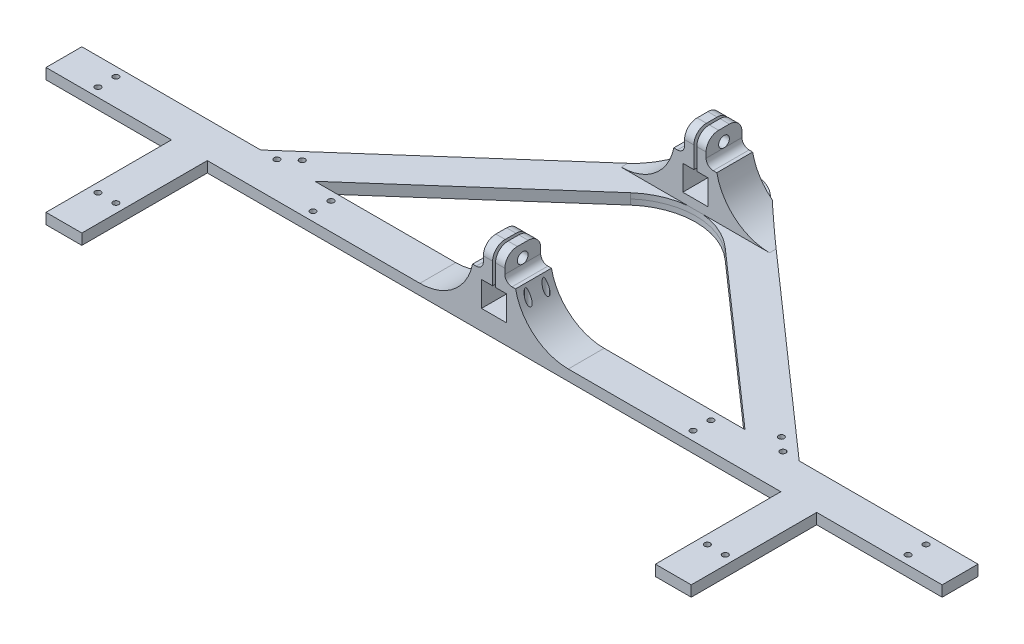
SolidWorks part; units mm, degrees
ref_plane "前视基准面" through (0, 0, 0) normal (0, 0, 1) x (1, 0, 0)
ref_plane "上视基准面" through (0, 0, 0) normal (0, 1, 0) x (1, 0, 0)
ref_plane "右视基准面" through (0, 0, 0) normal (1, 0, 0) x (0, 0, -1)
sketch "草图1" plane through (0, 0, 0) normal (0, 1, 0) x (1, 0, 0)
  line L1 (-125, 5) -> (125, 5)
  line L2 (-125, 5) -> (-125, -5)
  line L3 (-125, -5) -> (125, -5)
  line L4 (125, 5) -> (125, -5)
  line L5 (-125, 5) -> (125, -5) construction
  line L6 (-125, -5) -> (125, 5) construction
  point P0 (0, 0)
  dimension "D1" = 250
  dimension "D2" = 10
extrude "凸台-拉伸1" add sketch "草图1" along normal blind 1.5
sketch "草图22" plane through (0, 0, 0) normal (0, -1, 0) x (1, 0, 0)
  line L0 (0, 107.0541) -> (0, -222.8841) construction
  line L1 (0, 0) -> (-60, 0)
  line L2 (-125, 5) -> (125, 5) construction
  line L4 (125, -5) -> (-125, -5) construction
  line L5 (60, 0) -> (60, -5)
  line L6 (-60, -5) -> (0, -57.915)
  line L7 (0, -57.915) -> (60, -5)
  line L8 (-75.1186, -5) -> (0, -71.2484)
  line L9 (0, -71.2484) -> (75.1186, -5)
  line L10 (-60, -5) -> (-75.1186, -5)
  line L11 (60, -5) -> (75.1186, -5)
  line M16 (-125, -5) -> (125, -5)
  dimension "D1" = 60
  dimension "D2" = 80
  dimension "D3" = 10
extrude "凸台-拉伸10" add sketch "草图22" against normal blind 1.5 separate body contours L0 L6 L8 M16 | L7 L0 L9 M16
fillet "圆角1" radius 10 1 edges at (0, 0.75, -71.2484)
fillet "圆角2" radius 20 1 edges at (0, 0.75, -57.915)
sketch "草图24" plane through (0, 1.5, 0) normal (0, 1, 0) x (1, 0, 0)
  line L1 (-10, 5) -> (10, 5)
  line L2 (-10, 5) -> (-10, -5)
  line L3 (-10, -5) -> (10, -5)
  line L4 (10, 5) -> (10, -5)
  line L5 (-10, 5) -> (10, -5) construction
  line L6 (-10, -5) -> (10, 5) construction
  point P0 (0, 0)
  dimension "D1" = 20
  dimension "D2" = 10
extrude "凸台-拉伸11" add sketch "草图24" along normal blind 20
sketch "草图25" plane through (0, 0, 5) normal (0, 0, 1) x (1, 0, 0)
  line L1 (0, 23.6125) -> (0, -2.2867) construction
sketch "草图26" plane through (0, 1.5, 0) normal (0, 1, 0) x (1, 0, 0)
  line L0 (0, 141.3842) -> (0, -41.294) construction
  line L2 (-11, 61.1419) -> (11, 61.1419)
  line L3 (-11, 61.1419) -> (-11, 51.1419)
  line L4 (-11, 51.1419) -> (11, 51.1419)
  line L5 (11, 61.1419) -> (11, 51.1419)
  line L6 (-11, 61.1419) -> (11, 51.1419) construction
  line L7 (-11, 51.1419) -> (11, 61.1419) construction
  point P6 (0, 56.1419)
  dimension "D1" = 22
  dimension "D2" = 10
sketch "草图41" plane through (0, 0, 5) normal (0, 0, 1) x (1, 0, 0)
  line L0 (125, 0.75) -> (-129.8236, 0.75) construction
  line L1 (125, 1.5) -> (125, 0) construction
  line L2 (125, 0.75) -> (85, 0.75)
  line L4 (80, 1.5) -> (90, 1.5)
  line L5 (80, 1.5) -> (80, 0)
  line L6 (80, 0) -> (90, 0)
  line L7 (90, 1.5) -> (90, 0)
  line L8 (80, 1.5) -> (90, 0) construction
  line L9 (80, 0) -> (90, 1.5) construction
  dimension "D1" = 40
  dimension "D2" = 10
  dimension "D3" = 1.5
extrude "凸台-拉伸13" add sketch "草图41" along normal blind 35
sketch "草图42" plane through (0, 0, 5) normal (0, 0, 1) x (1, 0, 0)
  line L0 (-125, 0.75) -> (-85, 0.75)
  line L1 (-125, 1.5) -> (-125, 0) construction
  line L3 (-90, 1.5) -> (-80, 1.5)
  line L4 (-90, 1.5) -> (-90, 0)
  line L5 (-90, 0) -> (-80, 0)
  line L6 (-80, 1.5) -> (-80, 0)
  line L7 (-90, 1.5) -> (-80, 0) construction
  line L8 (-90, 0) -> (-80, 1.5) construction
  dimension "D1" = 40
  dimension "D2" = 10
  dimension "D3" = 1.5
extrude "凸台-拉伸14" add sketch "草图42" along normal blind 35
sketch "草图57" plane through (0, 0, 0) normal (0, -1, 0) x (-1, 0, 0)
  line L0 (125, -5) -> (90, -5)
  line L1 (90, -5) -> (90, -40)
  line L2 (90, -40) -> (80, -40)
  line L3 (80, -40) -> (80, -5)
  line L4 (80, -5) -> (-80, -5)
  line L5 (-80, -5) -> (-80, -40)
  line L6 (-80, -40) -> (-90, -40)
  line L7 (-90, -40) -> (-90, -5)
  line L8 (-90, -5) -> (-125, -5)
  line L9 (-125, -5) -> (-125, 5)
  line L10 (-125, 5) -> (-75.1186, 5)
  line L11 (-75.1186, 5) -> (-6.6144, 65.415)
  line L12 (-6.6144, 65.415) -> (0, 71.2484)
  line L13 (0, 71.2484) -> (6.6144, 65.415)
  line L14 (6.6144, 65.415) -> (75.1186, 5)
  line L15 (75.1186, 5) -> (125, 5)
  line L16 (125, 5) -> (125, -5)
  line L17 (60, 5) -> (-60, 5)
  line L18 (-60, 5) -> (0, 57.915)
  line L19 (0, 57.915) -> (60, 5)
extrude "凸台-拉伸15" add sketch "草图57" along normal blind 1.5
fillet "圆角5" radius 20 1 edges at (0, -0.75, -57.915)
fillet "圆角6" radius 10 1 edges at (0, -0.75, -71.2484)
sketch "草图58" plane through (0, -1.5, 0) normal (0, -1, 0) x (1, 0, 0)
  line L0 (0, 12.1149) -> (0, -11.1082) construction
  line L1 (0, 0) -> (7, 0)
  line L2 (7, 0) -> (7, 2.5)
  line L3 (7, 0) -> (7, -2.5)
  line L4 (127.0686, 0) -> (101.0767, 0) construction
  line L5 (125, 0) -> (113, 0)
  line L6 (125, -5) -> (125, 5) construction
  line L7 (113, 0) -> (113, 2.5)
  line L8 (113, 0) -> (113, -2.5)
  line L10 (-125, 5) -> (-125, -5)
  line L11 (125, 5) -> (125, -5)
  line L12 (0, 0) -> (53, 0)
  line L14 (53, 0) -> (53, 2.5)
  line L15 (53, 0) -> (53, -2.5)
  line L16 (-85, 40) -> (-85, 28)
  line L17 (-80, 40) -> (-90, 40) construction
  line L18 (-85, 28) -> (-87.5, 28)
  line L19 (-85, 28) -> (-82.5, 28)
  circle A0 centre (7, -2.5) radius 0.8
  circle A1 centre (7, 2.5) radius 0.8
  circle A2 centre (113, 2.5) radius 0.8
  circle A3 centre (113, -2.5) radius 0.8
  circle A4 centre (-113, -2.5) radius 0.8
  circle A5 centre (-113, 2.5) radius 0.8
  circle A6 centre (53, 2.5) radius 0.8
  circle A7 centre (53, -2.5) radius 0.8
  circle A8 centre (-53, -2.5) radius 0.8
  circle A9 centre (-53, 2.5) radius 0.8
  circle A10 centre (-82.5, 28) radius 0.8
  circle A11 centre (-87.5, 28) radius 0.8
  circle A12 centre (82.5, 28) radius 0.8
  circle A13 centre (87.5, 28) radius 0.8
  dimension "D4" = 1.6
  dimension "D5" = 1.6
  dimension "D9" = 1.6
  dimension "D10" = 1.6
  dimension "D15" = 1.6
  dimension "D16" = 1.6
  dimension "D20" = 1.6
  dimension "D21" = 1.6
  dimension "D1" = 7
  dimension "D2" = 2.5
  dimension "D3" = 2.5
  dimension "D6" = 12
  dimension "D7" = 2.5
  dimension "D8" = 2.5
  dimension "D11" = 250
  dimension "D12" = 53
  dimension "D13" = 2.5
  dimension "D14" = 2.5
  dimension "D17" = 12
  dimension "D18" = 2.5
  dimension "D19" = 2.5
extrude "切除-拉伸52" cut sketch "草图58" against normal through all
extrude "凸台-拉伸16" add sketch "草图26" along normal blind 20
sketch "草图59" plane through (0, 0, -61.1419) normal (0, 0, -1) x (-1, 0, 0)
  line L0 (0, 1.5376) -> (0, 4.0376)
  line L1 (0, 23.6125) -> (0, -2.2867) construction
  line L2 (0, 4.0376) -> (3.5, 4.0376)
  line L3 (3.5, 4.0376) -> (3.5, 11.0376)
  line L4 (3.5, 11.0376) -> (-3.5, 11.0376)
  line L5 (-3.5, 11.0376) -> (-3.5, 4.0376)
  line L6 (-3.5, 4.0376) -> (0, 4.0376)
  line L7 (0, 1.5376) -> (6, 1.5)
  line L8 (-11, 1.5) -> (11, 1.5) construction
  line L9 (6, 1.5) -> (6, 13.5)
  line L10 (6, 13.5) -> (-6, 13.5)
  line L11 (-6, 13.5) -> (-6, 1.5)
  line L12 (-6, 1.5) -> (0, 1.5376)
  line L14 (0, 13.5) -> (3, 13.5)
  line L18 (0, 13.5) -> (-3, 13.5)
  line L24 (0, 11.0376) -> (0.9278, 11.0376)
  line L26 (0, 13.5) -> (0.4, 13.5)
  line L27 (0, 13.5) -> (0, 20.5)
  line L28 (0, 20.5) -> (0.4, 20.5)
  line L29 (0.4, 13.5) -> (0.4, 20.5)
  line L30 (0, 13.5) -> (-0.4, 13.5)
  line L31 (0, 13.5) -> (0, 20.5)
  line L32 (0, 20.5) -> (-0.4, 20.5)
  line L33 (-0.4, 13.5) -> (-0.4, 20.5)
  line L34 (-0.4, 13.5) -> (0.4, 13.5)
  line L35 (-0.4, 13.5) -> (-0.4, 11.0376)
  line L36 (-0.4, 11.0376) -> (0.4, 11.0376)
  line L37 (0.4, 13.5) -> (0.4, 11.0376)
  line L38 (0, 13.5) -> (3, 13.5)
  line L39 (0, 13.5) -> (0, 20.5)
  line L40 (0, 20.5) -> (3, 20.5)
  line L41 (3, 13.5) -> (3, 20.5)
  line L42 (0, 13.5) -> (-3, 13.5)
  line L43 (0, 13.5) -> (0, 20.5)
  line L44 (0, 20.5) -> (-3, 20.5)
  line L45 (-3, 13.5) -> (-3, 20.5)
  line M21 (-11, 1.5) -> (11, 1.5)
  line M22 (11, 1.5) -> (11, 21.5)
  line M23 (11, 21.5) -> (-11, 21.5)
  line M24 (-11, 21.5) -> (-11, 1.5)
  dimension "D1" = 2.5
  dimension "D2" = 3.5
  dimension "D3" = 7
  dimension "D4" = 7
  dimension "D5" = 12
  dimension "D6" = 12
  dimension "D7" = 6
  dimension "D8" = 0.4
  dimension "D9" = 7
  dimension "D10" = 0.4
  dimension "D11" = 7
  dimension "D12" = 3
  dimension "D13" = 3
extrude "切除-拉伸53" cut sketch "草图59" against normal through all contours L10 L45 L44 L32 L28 L40 L41 L9 L11 M21 M22 M23 M24 | L5 L6 L2 L3 L4 L24 | L37 L14 L10 L35 L4 L24 | L33 L10 L27 L32 | L14 L29 L28 L27
fillet "圆角7" radius 15 2 edges at (6, 1.5, -56.1419) (-6, 1.5, -56.1419)
fillet "圆角8" radius 15 2 edges at (6, 1.5, 0) (-6, 1.5, 0)
fillet "圆角9" radius 3.5 8 edges at (-1.7, 20.5, 5) (1.7, 20.5, 5) (1.7, 20.5, -5) (-1.7, 20.5, -5) (-1.7, 20.5, -51.1419) (1.7, 20.5, -51.1419) (-1.7, 20.5, -61.1419) (1.7, 20.5, -61.1419)
sketch "草图60" plane through (-3, 0, 0) normal (-1, 0, 0) x (0, 0, 1)
  line L0 (-56.1419, 20.5) -> (-56.1419, 17) construction
  line L1 (-54.6419, 20.5) -> (-57.6419, 20.5) construction
  circle A0 centre (-56.1419, 17) radius 1.5
  dimension "D2" = 3
  dimension "D1" = 3.5
extrude "切除-拉伸54" cut sketch "草图60" against normal through all
sketch "草图61" plane through (-3, 0, 0) normal (-1, 0, 0) x (0, 0, 1)
  line L0 (0, 20.5) -> (0, 17) construction
  line L1 (1.5, 20.5) -> (-1.5, 20.5) construction
  circle A0 centre (0, 17) radius 1.5
  dimension "D2" = 3
  dimension "D1" = 3.5
extrude "切除-拉伸55" cut sketch "草图61" against normal through all
fillet "圆角10" radius 2 4 edges at (3, 13.5, -56.1419) (3, 13.5, 0) (-3, 13.5, 0) (-3, 13.5, -56.1419)
sketch "草图63" plane through (0, 1.5, 0) normal (0, 1, 0) x (1, 0, 0)
  line L0 (72.4633, 3.3417) -> (59.0753, 15.1489) construction
  line L1 (75.1186, 5) -> (64.3471, 14.4995) construction
  line L2 (20.6969, 52.9954) -> (75.1186, 5) construction
  line L3 (75.1186, 5) -> (70.583, 5) construction
  line L4 (0, -22.5098) -> (0, 28.2143) construction
  circle A0 centre (70.583, 5) radius 0.8
  circle A1 centre (66.833, 8.3072) radius 0.8
  circle A2 centre (-66.833, 8.3072) radius 0.8
  circle A3 centre (-70.583, 5) radius 0.8
  point P10 (66.833, 8.3072)
  dimension "D2" = 1.6
  dimension "D4" = 1.6
  dimension "D1" = 3
  dimension "D3" = 5
extrude "切除-拉伸56" cut sketch "草图63" against normal through all
